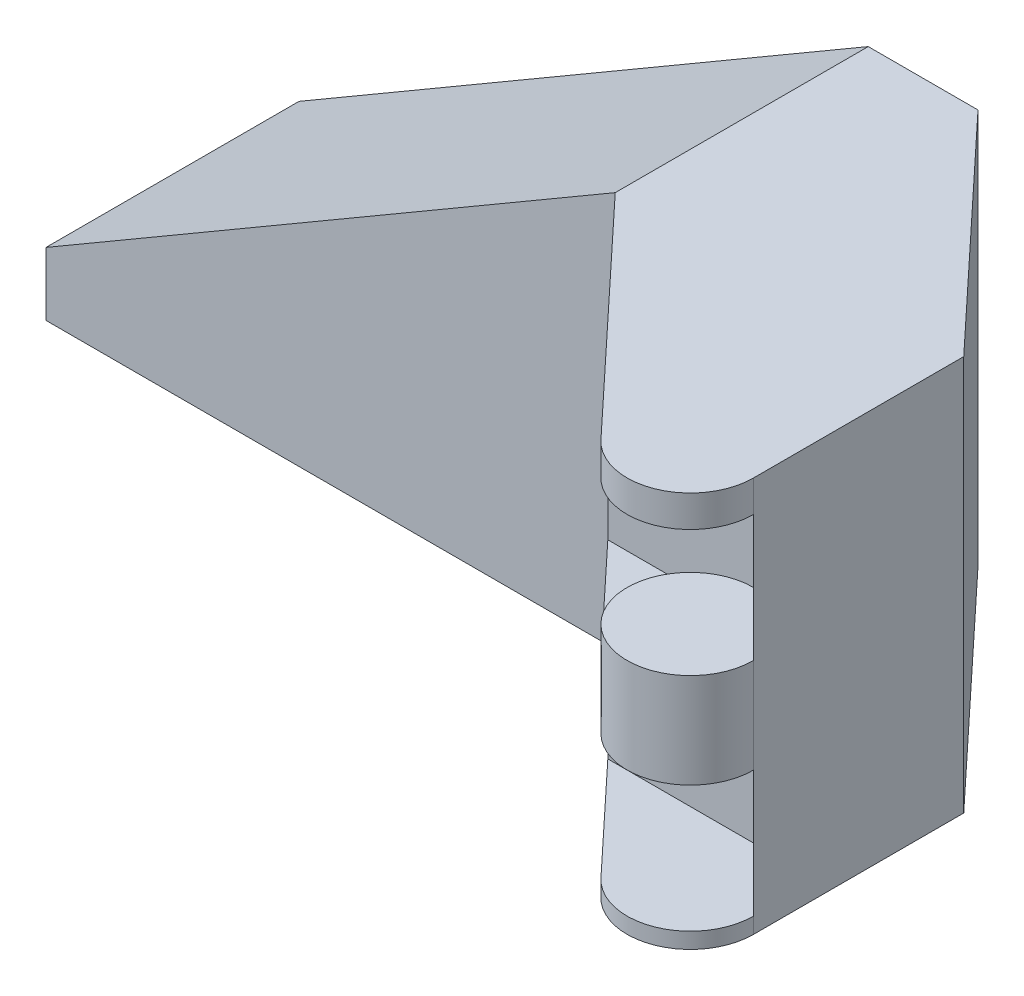
SolidWorks part; units mm, degrees
ref_plane "Front" through (0, 0, 0) normal (0, 0, 1) x (1, 0, 0)
ref_plane "Top" through (0, 0, 0) normal (0, 1, 0) x (1, 0, 0)
ref_plane "Right" through (0, 0, 0) normal (1, 0, 0) x (0, 0, -1)
sketch "Sketch1" plane through (0, 0, 0) normal (0, 1, 0) x (1, 0, 0)
  line L0 (-12.7, 0) -> (-69.85, 0)
  line L1 (-69.85, 0) -> (-69.85, 25.4)
  line L2 (-69.85, 25.4) -> (-1.6788, 25.4)
  line L3 (25.4, 25.4) -> (25.4, 0) construction
  line L4 (12.7, -24.2094) -> (0, -24.2094) construction
  line L5 (0, -13.5775) -> (0, 0) construction
  line L6 (12.7, -24.2094) -> (12.7, -17.8594) construction
  line L8 (8.0625, -22.1971) -> (-12.7, 0)
  line L9 (25.4, 0) -> (25.4, -24.2094) construction
  line L10 (25.4, -24.2094) -> (12.7, -24.2094) construction
  line L11 (0, -24.2094) -> (0, -13.5775) construction
  line L12 (0, 0) -> (-12.7, 0) construction
  line L13 (0, 0) -> (25.4, 0) construction
  line L15 (-1.6788, 25.4) -> (25.4, 25.4) construction
  line L16 (19.05, -17.8594) -> (19.05, 3.2389)
  line L17 (19.05, 3.2389) -> (-1.6788, 25.4)
  line L18 (-12.7, 0) -> (5.85, 17.3511) construction
  arc A0 (8.0625, -22.1971) -> (19.05, -17.8594) centre (12.7, -17.8594) ccw
  arc A1 (19.05, -17.8594) -> (8.0625, -22.1971) centre (12.7, -17.8594) ccw construction
  point P13 (0, 0)
  point P17 (0, 0)
  point P19 (0, 0)
  dimension "D2" = 12.7
  dimension "D1" = 25.4
  dimension "D3" = 17.8594
  dimension "D4" = 69.85
  dimension "D5" = 25.4
  dimension "D6" = 57.15
extrude "Boss-Extrude1" add sketch "Sketch1" along normal blind 39.6875
ref_plane "Plane1" through (0, 36.5125, 0) normal (0, 1, 0) x (1, 0, 0)
sketch "Sketch2" plane through (0, 36.5125, 0) normal (0, 1, 0) x (1, 0, 0)
  line L0 (12.7, -11.5094) -> (-1.9345, -11.5094)
  line L1 (-12.7, 0) -> (8.0625, -22.1971) construction
  line L2 (-1.9345, -11.5094) -> (8.0625, -22.1971)
  line L3 (-12.7, 0) -> (-1.9345, -11.5094) construction
  arc A0 (8.0625, -22.1971) -> (12.7, -11.5094) centre (12.7, -17.8594) ccw
  arc A1 (8.0625, -22.1971) -> (19.05, -17.8594) centre (12.7, -17.8594) ccw construction
  arc A2 (12.7, -11.5094) -> (8.0625, -22.1971) centre (12.7, -17.8594) ccw construction
extrude "Cut-Extrude1" cut sketch "Sketch2" against normal blind 12.7
ref_plane "Plane2" through (0, 14.2875, 0) normal (0, 1, 0) x (1, 0, 0)
sketch "Sketch3" plane through (0, 14.2875, 0) normal (0, 1, 0) x (1, 0, 0)
  line L0 (12.7, -11.5094) -> (-1.9345, -11.5094)
  line L1 (-12.7, 0) -> (8.0625, -22.1971) construction
  line L2 (-1.9345, -11.5094) -> (8.0625, -22.1971)
  line L3 (-12.7, 0) -> (-1.9345, -11.5094) construction
  arc A0 (8.0625, -22.1971) -> (12.7, -11.5094) centre (12.7, -17.8594) ccw
  arc A1 (8.0625, -22.1971) -> (19.05, -17.8594) centre (12.7, -17.8594) ccw construction
  arc A2 (12.7, -11.5094) -> (8.0625, -22.1971) centre (12.7, -17.8594) ccw construction
extrude "Cut-Extrude2" cut sketch "Sketch3" against normal blind 12.7
sketch "Sketch4" plane through (0, 23.8125, 0) normal (0, 1, 0) x (1, 0, 0)
  line L0 (12.7, -11.5094) -> (-1.9345, -11.5094)
  line L1 (-12.7, 0) -> (8.0625, -22.1971) construction
  line L2 (-1.9345, -11.5094) -> (8.0625, -22.1971)
  line L3 (-12.7, 0) -> (-1.9345, -11.5094) construction
  arc A0 (12.7, -11.5094) -> (8.0625, -22.1971) centre (12.7, -17.8594) ccw
  arc A1 (8.0625, -22.1971) -> (19.05, -17.8594) centre (12.7, -17.8594) ccw construction
  arc A2 (8.0625, -22.1971) -> (12.7, -11.5094) centre (12.7, -17.8594) ccw construction
extrude "Cut-Extrude3" cut sketch "Sketch4" against normal blind 3.175
extrude "Cut-Extrude4" cut sketch "Sketch4<2>" along normal blind 3.175 from surface starting at face at (10.1672, 14.2875, 16.3744)
sketch "Sketch4<2>" plane through (0, 23.8125, 0) normal (0, 1, 0) x (1, 0, 0) same geometry as "Sketch4"
sketch "Sketch5" plane through (0, 0, -25.4) normal (0, 0, -1) x (-1, 0, 0)
  line L0 (69.85, 0) -> (69.85, 6.35) construction
  line L1 (69.85, 39.6875) -> (69.85, 0) construction
  line L2 (69.85, 6.35) -> (12.7, 39.6875)
  line L3 (12.7, 39.6875) -> (-8.0625, 39.6875) construction
  line L4 (12.7, 39.6875) -> (69.85, 39.6875)
  line L5 (69.85, 39.6875) -> (69.85, 6.35)
  line L6 (12.7, 39.6875) -> (12.7, 0) construction
  line L8 (12.7, 0) -> (-8.0625, 0) construction
  line L10 (12.7, 39.6875) -> (12.7, 0) construction
  point P11 (20.3326, 39.6875)
  point P13 (16.1086, 0)
  dimension "D1" = 6.35
extrude "Cut-Extrude5" cut sketch "Sketch5" against normal through all
